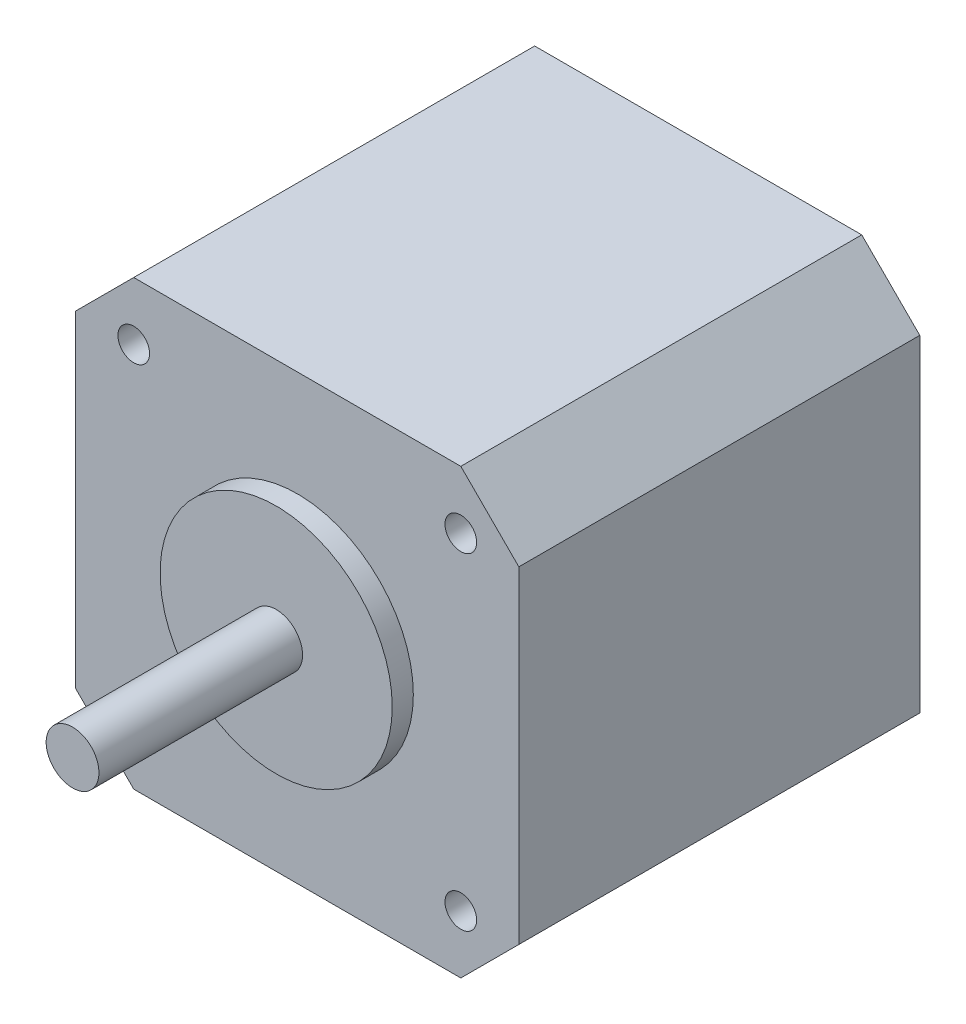
SolidWorks part; units mm, degrees
ref_plane "Front Plane" through (0, 0, 0) normal (0, 0, 1) x (1, 0, 0)
ref_plane "Top Plane" through (0, 0, 0) normal (0, 1, 0) x (1, 0, 0)
ref_plane "Right Plane" through (0, 0, 0) normal (1, 0, 0) x (0, 0, -1)
sketch "Sketch1" plane through (0, 0, 0) normal (0, 0, 1) x (1, 0, 0)
  line L0 (-15.5, -21) -> (15.5, -21)
  line L1 (-21, -21) -> (21, -21)
  line L2 (-21, -21) -> (-21, 21)
  line L3 (-21, 21) -> (21, 21)
  line L4 (21, -21) -> (21, 21)
  line L5 (-21, -21) -> (21, 21) construction
  line L6 (-21, 21) -> (21, -21) construction
  line L7 (21, -15.5) -> (21, 15.5)
  line L8 (15.5, 21) -> (-15.5, 21)
  line L9 (-21, -15.5) -> (-21, 15.5)
  line L10 (-21, 15.5) -> (-15.5, 21)
  line L11 (15.5, 21) -> (21, 15.5)
  line L12 (15.5, -21) -> (21, -15.5)
  line L13 (-15.5, -21) -> (-21, -15.5)
  point P0 (0, 0)
  point P9 (0, -21)
  point P12 (21, 0)
  point P15 (0, 21)
  point P18 (-21, 0)
  dimension "D1" = 41.9999
  dimension "D2" = 41.9999
  dimension "D3" = 30.9999
  dimension "D4" = 30.9999
  dimension "D5" = 30.9999
  dimension "D6" = 30.9999
extrude "Boss-Extrude1" add sketch "Sketch1" along normal blind 37.9999 contours L13 L0 L12 L4 L11 L3 L10 L2 region at (0, 0, 0)
sketch "Sketch2" plane through (0, 0, 37.9999) normal (0, 0, 1) x (1, 0, 0)
  circle A0 centre (0, 0) radius 11
  dimension "D1" = 22
extrude "Boss-Extrude2" add sketch "Sketch2" along normal blind 2
sketch "Sketch3" plane through (0, 0, 39.9999) normal (0, 0, 1) x (1, 0, 0)
  circle A0 centre (0, 0) radius 2.5
  dimension "D1" = 5
extrude "Boss-Extrude3" add sketch "Sketch3" along normal blind 19.3
sketch "Sketch4" plane through (0, 0, 37.9999) normal (0, 0, 1) x (1, 0, 0)
  line L1 (15.5, -15.5) -> (-15.5, -15.5)
  line L2 (15.5, -15.5) -> (15.5, 15.5)
  line L3 (15.5, 15.5) -> (-15.5, 15.5)
  line L4 (-15.5, -15.5) -> (-15.5, 15.5)
  line L5 (15.5, -15.5) -> (-15.5, 15.5) construction
  line L6 (15.5, 15.5) -> (-15.5, -15.5) construction
  circle A0 centre (-15.5, 15.5) radius 1.5
  circle A1 centre (-15.5, -15.5) radius 1.5
  circle A2 centre (15.5, -15.5) radius 1.5
  circle A3 centre (15.5, 15.5) radius 1.5
  point P0 (0, 0)
  dimension "D3" = 3
  dimension "D4" = 3
  dimension "D5" = 3
  dimension "D6" = 3
  dimension "D1" = 30.9999
  dimension "D2" = 30.9999
extrude "Cut-Extrude1" cut sketch "Sketch4" against normal blind 4 contours L4 A0 L3 | L3 A0 L4 | L4 A1 L1 | L1 A1 L4 | L2 A2 L1 | L1 A2 L2 | L2 A3 L3 | L3 A3 L2 region at (-15.7122, -15.7122, 37.9999) region at (-14.8634, -14.8634, 37.9999) region at (14.8634, -14.8634, 37.9999) region at (15.7122, -15.7122, 37.9999) region at (-15.7122, 15.7122, 37.9999) region at (-14.8634, 14.8634, 37.9999) region at (14.8634, 14.8634, 37.9999) region at (15.7122, 15.7122, 37.9999)
sketch "Sketch6" plane through (0, 0, 0) normal (0, 0, -1) x (-1, 0, 0)
  circle A0 centre (0, 0) radius 2.5
  dimension "D1" = 5
